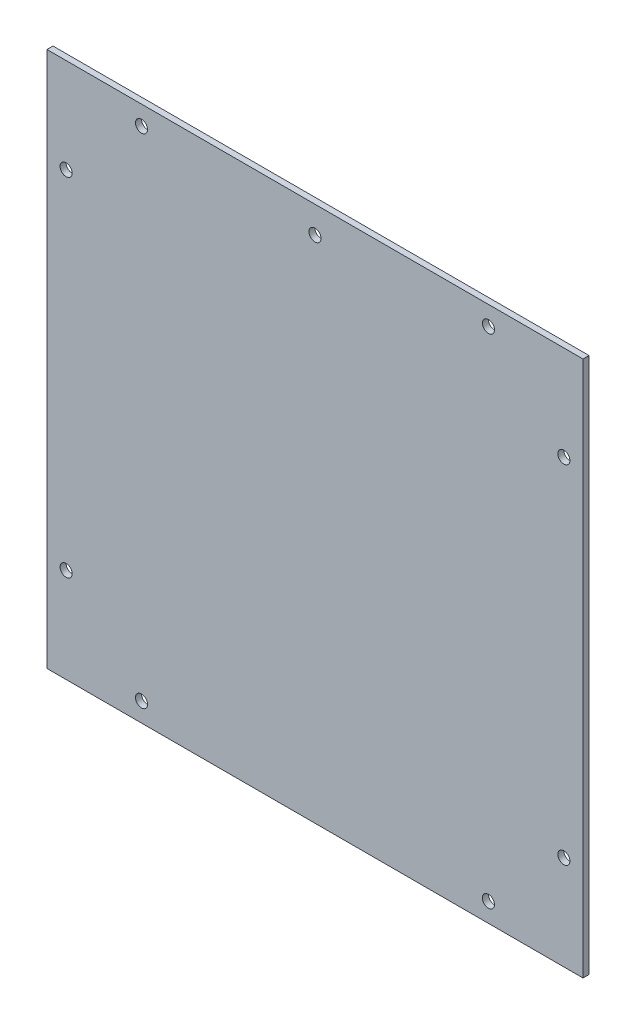
SolidWorks part; units mm, degrees
material "5052-O"
ref_plane "Front Plane" through (0, 0, 0) normal (0, 0, 1) x (1, 0, 0)
ref_plane "Top Plane" through (0, 0, 0) normal (0, 1, 0) x (1, 0, 0)
ref_plane "Right Plane" through (0, 0, 0) normal (1, 0, 0) x (0, 0, -1)
sketch "Sketch2" plane through (0, 0, 0) normal (0, 0, 1) x (1, 0, 0)
  line L1 (-177.7, 177.7) -> (177.7, 177.7)
  line L2 (-177.7, 177.7) -> (-177.7, -177.7)
  line L3 (-177.7, -177.7) -> (177.7, -177.7)
  line L4 (177.7, 177.7) -> (177.7, -177.7)
  circle A1 centre (-115, 165) radius 4
  circle A2 centre (-165, 115) radius 4
  circle A3 centre (-165, -115) radius 4
  circle A4 centre (-115, -165) radius 4
  circle A5 centre (115, -165) radius 4
  circle A6 centre (165, -115) radius 4
  circle A7 centre (165, 115) radius 4
  circle A8 centre (115, 165) radius 4
  circle A9 centre (0, 160) radius 4
  dimension "D5" = 8
  dimension "D6" = 8
  dimension "D7" = 8
  dimension "D8" = 8
  dimension "D9" = 8
  dimension "D10" = 8
  dimension "D11" = 8
  dimension "D12" = 8
  dimension "D13" = 8
  dimension "D1" = 355.4
  dimension "D2" = 355.4
  dimension "D3" = 177.7
  dimension "D4" = 177.7
extrude "Boss-Extrude2" add sketch "Sketch2" along normal blind 4
